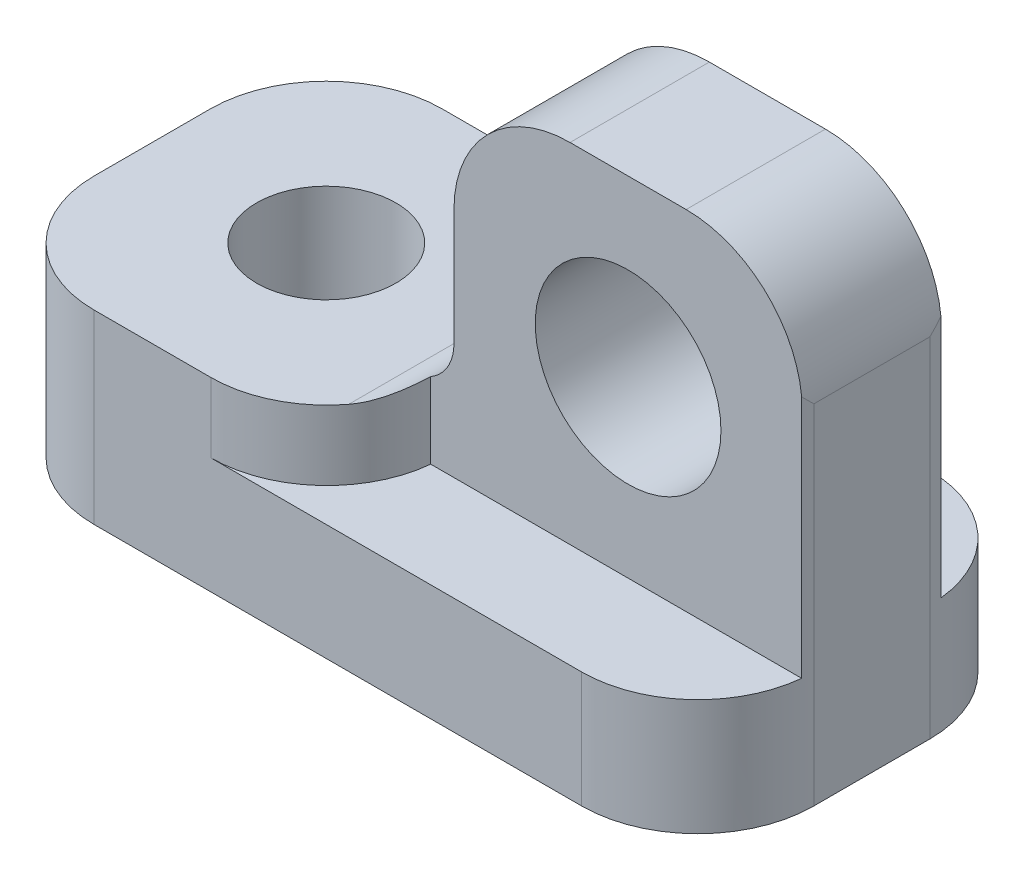
SolidWorks part; units mm, degrees
ref_plane "Front Plane" through (0, 0, 0) normal (0, 0, 1) x (1, 0, 0)
ref_plane "Top Plane" through (0, 0, 0) normal (0, 1, 0) x (1, 0, 0)
ref_plane "Right Plane" through (0, 0, 0) normal (1, 0, 0) x (0, 0, -1)
sketch "Sketch1" plane through (0, 0, 0) normal (0, 1, 0) x (1, 0, 0)
  line L0 (0, 7.5) -> (31, 7.5) construction
  line L1 (0, 0) -> (31, 0)
  line L2 (0, 0) -> (0, 15)
  line L3 (0, 15) -> (31, 15)
  line L4 (31, 0) -> (31, 15)
  dimension "D1" = 15
  dimension "D2" = 31
extrude "Boss-Extrude1" add sketch "Sketch1" along normal blind 5
sketch "Sketch2" plane through (0, 5, 0) normal (0, 1, 0) x (1, 0, 0)
  line L0 (0, 0) -> (31, 0) construction
  line L1 (0, 15) -> (15, 15)
  line L2 (0, 15) -> (0, 0)
  line L3 (0, 0) -> (15, 0)
  line L4 (15, 15) -> (15, 0)
  line L5 (7.5, 15) -> (7.5, 0) construction
  line L7 (0, 7.5) -> (15, 7.5) construction
  dimension "D1" = 15
extrude "Boss-Extrude2" add sketch "Sketch2" along normal blind 3
sketch "Sketch3" plane through (0, 5, 0) normal (0, 1, 0) x (1, 0, 0)
  line L0 (15, 7.5) -> (31, 7.5) construction
  line L1 (15, 0) -> (15, 15) construction
  line L2 (31, 0) -> (31, 15) construction
  line L8 (16, 10.5) -> (31, 10.5)
  line L9 (16, 10.5) -> (16, 4.5)
  line L10 (16, 4.5) -> (31, 4.5)
  line L11 (31, 10.5) -> (31, 4.5)
  dimension "D1" = 3
  dimension "D2" = 6
  dimension "D3" = 15
extrude "Boss-Extrude3" add sketch "Sketch3" along normal blind 15
sketch "Sketch4" plane through (0, 5, 0) normal (0, 1, 0) x (1, 0, 0)
  line L0 (15, 0) -> (15, 15) construction
  line L1 (16, 10.5) -> (15, 10.5)
  line L2 (16, 10.5) -> (16, 4.5)
  line L3 (16, 4.5) -> (15, 4.5)
  line L4 (15, 10.5) -> (15, 4.5)
extrude "rib" add sketch "Sketch4" along normal blind 3
sketch "Sketch5" plane through (0, 0, -4.5) normal (0, 0, 1) x (1, 0, 0)
  line L0 (31, 12.5) -> (16, 12.5) construction
  line L1 (31, 20) -> (31, 5) construction
  line L2 (16, 20) -> (16, 8) construction
  circle A0 centre (23.5, 12.5) radius 4
  dimension "D1" = 8
sketch "Sketch6" plane through (0, 8, 0) normal (0, 1, 0) x (1, 0, 0)
  line L0 (7.5, 15) -> (7.5, 0) construction
  line L1 (15, 15) -> (0, 15) construction
  line L2 (0, 0) -> (15, 0) construction
  circle A0 centre (7.5, 7.5) radius 3
  dimension "D1" = 6
extrude "Cut-Extrude1" cut sketch "Sketch5" against normal through all
extrude "Cut-Extrude2" cut sketch "Sketch6" against normal offset from surface (7.8 mm away) 0.2 up to face at (15.5, 0, -7.5)
fillet "Fillet1" radius 5 2 edges at (31, 20, -7.5) (16, 20, -7.5)
fillet "Fillet2" radius 5 6 edges at (31, 2.5, -15) (31, 2.5, 0) (0, 4, 0) (0, 4, -15)
fillet "Fillet3" radius 2 1 edges at (16, 8, -7.5)
